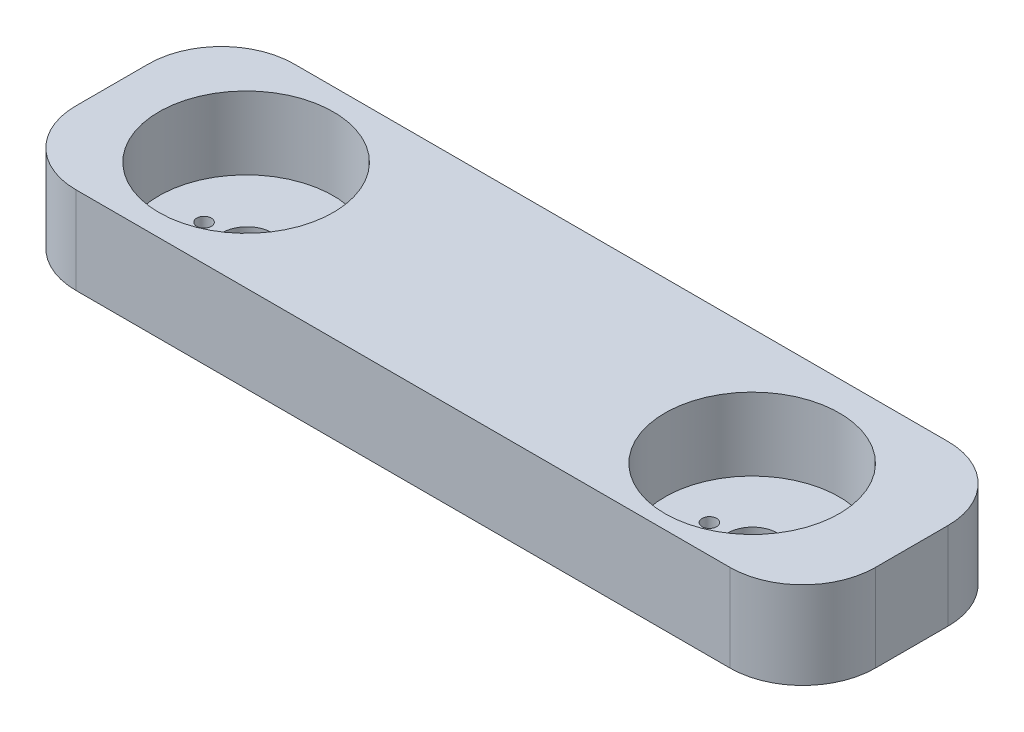
SolidWorks part; units mm, degrees
ref_plane "Front Plane" through (0, 0, 0) normal (0, 0, 1) x (1, 0, 0)
ref_plane "Top Plane" through (0, 0, 0) normal (0, 1, 0) x (1, 0, 0)
ref_plane "Right Plane" through (0, 0, 0) normal (1, 0, 0) x (0, 0, -1)
sketch "Sketch1" plane through (0, 0, 0) normal (0, 1, 0) x (1, 0, 0)
  line L1 (-49.6146, 18.5384) -> (60.3854, 18.5384)
  line L2 (-49.6146, 18.5384) -> (-49.6146, -11.4616)
  line L3 (-49.6146, -11.4616) -> (60.3854, -11.4616)
  line L4 (60.3854, 18.5384) -> (60.3854, -11.4616)
  dimension "D1" = 110
  dimension "D2" = 30
extrude "Boss-Extrude1" add sketch "Sketch1" along normal blind 12
fillet "Fillet1" radius 10 2 edges at (-49.6146, 6, -18.5384) (-49.6146, 6, 11.4616)
fillet "Fillet2" radius 10 2 edges at (60.3854, 6, -18.5384) (60.3854, 6, 11.4616)
sketch "Sketch9" plane through (0, 12, 0) normal (0, 1, 0) x (1, 0, 0)
  line L0 (-39.6146, -11.4616) -> (50.3854, -11.4616) construction
  circle A0 centre (-31.1958, 3.5384) radius 12
  dimension "D1" = 15
extrude "Cut-Extrude5" cut sketch "Sketch9" against normal blind 10
sketch "Sketch13" plane through (70.6968, 12, 1.0722) normal (0, 1, 0) x (1, 0, 0)
  circle A0 centre (-31.1958, 3.5384) radius 12
extrude "Cut-Extrude7" cut sketch "Sketch13" against normal blind 10
sketch "Sketch15" plane through (70.6968, 2, 1.0722) normal (0, 1, 0) x (1, 0, 0)
  circle A0 centre (-31.1477, 3.5384) radius 3.43
  circle A1 centre (-25.2177, 3.5384) radius 1
  circle A2 centre (-37.0777, 3.5384) radius 1
  dimension "D2" = 2.5
  dimension "D3" = 2.5
extrude "Cut-Extrude8" cut sketch "Sketch15" against normal through all
sketch "Sketch16" plane through (70.6968, 2, 1.0722) normal (0, 1, 0) x (1, 0, 0)
  circle A0 centre (-101.6996, 4.5567) radius 3.43
  circle A1 centre (-95.7696, 4.5567) radius 1
  circle A2 centre (-107.6296, 4.5567) radius 1
  dimension "D2" = 2.5
  dimension "D3" = 2.5
extrude "Cut-Extrude9" cut sketch "Sketch16" against normal through all
